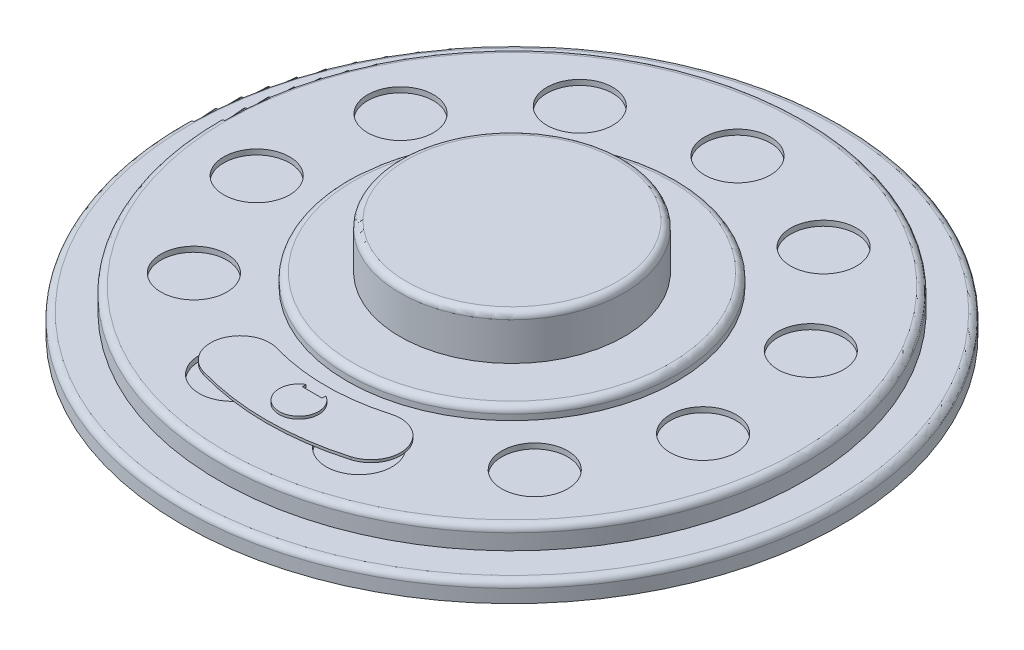
SolidWorks part; units mm, degrees
ref_plane "Front Plane" through (0, 0, 0) normal (0, 0, 1) x (1, 0, 0)
ref_plane "Top Plane" through (0, 0, 0) normal (0, 1, 0) x (1, 0, 0)
ref_plane "Right Plane" through (0, 0, 0) normal (1, 0, 0) x (0, 0, -1)
sketch "Sketch1" plane through (0, 0, 0) normal (0, 0, 1) x (1, 0, 0)
  line L0 (25, 0.0213) -> (25, 1.0209)
  line L3 (22.2127, 1.5209) -> (22.2127, 2.7018)
  line L5 (0, 0) -> (0, 7.5)
  line L7 (0, 7.5) -> (8, 7.5)
  line L9 (8.5, 4.1315) -> (12, 4.1315)
  line L10 (24.5, 1.5209) -> (22.2127, 1.5209)
  line L11 (21.7127, 3.2018) -> (12.5, 3.2018)
  line L12 (12.5, 3.6315) -> (12.5, 3.2018)
  line L13 (0, 0) -> (25, 0.0213)
  line L14 (8.5, 4.1315) -> (8.5, 7)
  arc A0 (25, 1.0209) -> (24.5, 1.5209) centre (24.5, 1.0209) ccw
  arc A3 (21.7127, 3.2018) -> (22.2127, 2.7018) centre (21.7127, 2.7018) cw
  arc A4 (12.5, 3.6315) -> (12, 4.1315) centre (12, 3.6315) ccw
  arc A7 (8, 7.5) -> (8.5, 7) centre (8, 7) cw
  dimension "D2" = 0.5
  dimension "D3" = 25
  dimension "D4" = 1.5
  dimension "D1" = 7.5
revolve "Revolve1" add sketch "Sketch1" angle 360 about L5
shell "Shell1" thickness 0.7 removed face at (0, 0.0213, -25)
ref_plane "Plane1" through (0, 12, 0) normal (0, 1, 0) x (1, 0, 0)
sketch "Sketch2" plane through (0, 12, 0) normal (0, 1, 0) x (1, 0, 0)
  line L0 (0, 21.7127) -> (0, 12.5) construction
  circle A16 centre (0, 0) radius 17.1064 construction
  circle A17 centre (0, 17.1064) radius 2.5
  circle A18 centre (9.2484, 14.3908) radius 2.5
  circle A19 centre (15.5605, 7.1062) radius 2.5
  circle A20 centre (16.9323, -2.4345) radius 2.5
  circle A21 centre (12.9281, -11.2023) radius 2.5
  circle A22 centre (4.8194, -16.4134) radius 2.5
  circle A23 centre (-4.8194, -16.4134) radius 2.5
  circle A24 centre (-12.9281, -11.2023) radius 2.5
  circle A25 centre (-16.9323, -2.4345) radius 2.5
  circle A26 centre (-15.5605, 7.1062) radius 2.5
  circle A27 centre (-9.2484, 14.3908) radius 2.5
  circle A28 centre (0, 0) radius 21.7127 construction
  circle A29 centre (0, 0) radius 12.5 construction
  point P28 (0, 0)
  point P33 (0, 0)
  point P34 (-9.6575, 14.1195)
  point P35 (-15.5628, 7.1013)
  dimension "D1" = 5
  dimension "D2" = 11
extrude "Cut-Extrude1" cut sketch "Sketch2" against normal through all
sketch "Sketch4" plane through (0, 0.8209, 0) normal (0, -1, 0) x (1, 0, 0)
  circle A0 centre (0, 0) radius 24.3 construction
  circle A1 centre (0, 0) radius 22.8
  circle A3 centre (0, 0) radius 24.3
  dimension "D1" = 1.5
extrude "Boss-Extrude1" add sketch "Sketch4" along normal blind 0.8 separate body
sketch "Sketch6" plane through (0, 0, 0) normal (0, 0, 1) x (1, 0, 0)
  line L5 (7.6314, 4.6292) -> (-7.8388, 4.6292) construction
ref_axis "Axis2" through (7.6314, 4.6292, 0) along (-1, 0, 0)
ref_plane "Plane2" through (0, 4.2775, 1.2266) normal (0, 0.9613, 0.2756) x (-1, 0, 0)
sketch "Sketch18" plane through (0, 0, 0) normal (0, 0, 1) x (1, 0, 0)
  line L0 (8.1, 3.7315) -> (8.1, 7)
  line L1 (8, 7.1) -> (0.4, 7.1)
  line L2 (0.4, 7.1) -> (0.4, 0.4003)
  line L3 (0.4, 0.4003) -> (24.6, 0.4209)
  line L4 (24.6, 0.4209) -> (24.6, 1.0209)
  line L5 (24.5, 1.1209) -> (21.8127, 1.1209)
  line L6 (21.8127, 1.1209) -> (21.8127, 2.7018)
  line L7 (21.7127, 2.8018) -> (12.1, 2.8018)
  line L8 (12.1, 2.8018) -> (12.1, 3.6315)
  line L9 (12, 3.7315) -> (8.1, 3.7315)
  line L10 (8.5, 4.1315) -> (8.5, 7)
  line L11 (12, 4.1315) -> (8.5, 4.1315)
  line L12 (12.5, 3.2018) -> (12.5, 3.6315)
  line L13 (21.7127, 3.2018) -> (12.5, 3.2018)
  line L14 (22.2127, 1.5209) -> (22.2127, 2.7018)
  line L15 (24.5, 1.5209) -> (22.2127, 1.5209)
  line L16 (25, 0.0213) -> (25, 1.0209)
  line L17 (0, 0) -> (25, 0.0213)
  line L18 (0, 7.5) -> (0, 0)
  line L19 (8, 7.5) -> (0, 7.5)
  line L20 (8.5, 4.1315) -> (8.5, 7) construction
  line L21 (12, 4.1315) -> (8.5, 4.1315) construction
  line L22 (12.5, 3.2018) -> (12.5, 3.6315) construction
  line L23 (21.7127, 3.2018) -> (12.5, 3.2018) construction
  line L24 (22.2127, 1.5209) -> (22.2127, 2.7018) construction
  line L25 (24.5, 1.5209) -> (22.2127, 1.5209) construction
  line L26 (25, 0.0213) -> (25, 1.0209) construction
  line L27 (0, 0) -> (25, 0.0213) construction
  line L28 (0, 7.5) -> (0, 0) construction
  line L29 (8, 7.5) -> (0, 7.5) construction
  line L30 (0, 0) -> (0, -1.2858) construction
  arc A0 (8.1, 7) -> (8, 7.1) centre (8, 7) ccw
  arc A1 (24.6, 1.0209) -> (24.5, 1.1209) centre (24.5, 1.0209) ccw
  arc A2 (21.8127, 2.7018) -> (21.7127, 2.8018) centre (21.7127, 2.7018) ccw
  arc A3 (12.1, 3.6315) -> (12, 3.7315) centre (12, 3.6315) ccw
  arc A4 (12.5, 3.6315) -> (12, 4.1315) centre (12, 3.6315) ccw
  arc A5 (22.2127, 2.7018) -> (21.7127, 3.2018) centre (21.7127, 2.7018) ccw
  arc A6 (25, 1.0209) -> (24.5, 1.5209) centre (24.5, 1.0209) ccw
  arc A7 (8.5, 7) -> (8, 7.5) centre (8, 7) ccw
  arc A8 (12.5, 3.6315) -> (12, 4.1315) centre (12, 3.6315) ccw construction
  arc A9 (22.2127, 2.7018) -> (21.7127, 3.2018) centre (21.7127, 2.7018) ccw construction
  arc A10 (25, 1.0209) -> (24.5, 1.5209) centre (24.5, 1.0209) ccw construction
  arc A11 (8.5, 7) -> (8, 7.5) centre (8, 7) ccw construction
  dimension "D1" = 0
  dimension "D2" = 0.4
revolve "Revolve2" add sketch "Sketch18" angle 360 about L30
sketch "Sketch8" plane through (0, 3.2018, 1.7562) normal (0, 1, 0) x (1, 0, 0)
  circle A1 centre (0, -14.4073) radius 1.5
  point P0 (-4, -13.9498)
extrude "Cut-Extrude2" cut sketch "Sketch8" against normal through all both and the other way through all
sketch "Sketch9" plane through (0, 3.2018, 1.7562) normal (0, 1, 0) x (1, 0, 0)
  circle A1 centre (0, -14.4073) radius 1.5
  circle A2 centre (0, -14.4073) radius 2
  dimension "D1" = 0.5
extrude "Boss-Extrude3" add sketch "Sketch9" along normal blind 0.2
sketch "Sketch10" plane through (0, 3.4018, 0) normal (0, 1, 0) x (1, 0, 0)
  arc A0 (-4.4339, -13.3944) -> (4.2316, -13.3944) centre (-0.1011, 1.4878) ccw
  arc A1 (-5.6917, -17.715) -> (5.4895, -17.715) centre (-0.1011, 1.4878) ccw
  arc A8 (-4.4339, -13.3944) -> (-5.6917, -17.715) centre (-5.0628, -15.5547) ccw
  arc A10 (5.4895, -17.715) -> (4.2316, -13.3944) centre (4.8606, -15.5547) ccw
extrude "Boss-Extrude4" add sketch "Sketch10" along normal blind 0.2
sketch "Sketch11" plane through (0, 3.6018, 0) normal (0, 1, 0) x (1, 0, 0)
  circle A0 centre (0, -16.1635) radius 1.5 construction
  circle A1 centre (0, -16.1635) radius 1.5
extrude "Boss-Extrude5" add sketch "Sketch11" along normal blind 0.2
sketch "Sketch12" plane through (0, 3.8018, 0) normal (0, 1, 0) x (1, 0, 0)
  line L2 (-0.75, -15.1573) -> (0.75, -15.1573)
  line L3 (-0.75, -15.1573) -> (-0.75, -13.6573)
  line L4 (-0.75, -13.6573) -> (0.75, -13.6573)
  line L5 (0.75, -15.1573) -> (0.75, -13.6573)
  point P7 (0, -14.4073)
extrude "Cut-Extrude3" cut sketch "Sketch12" against normal blind 0.2
